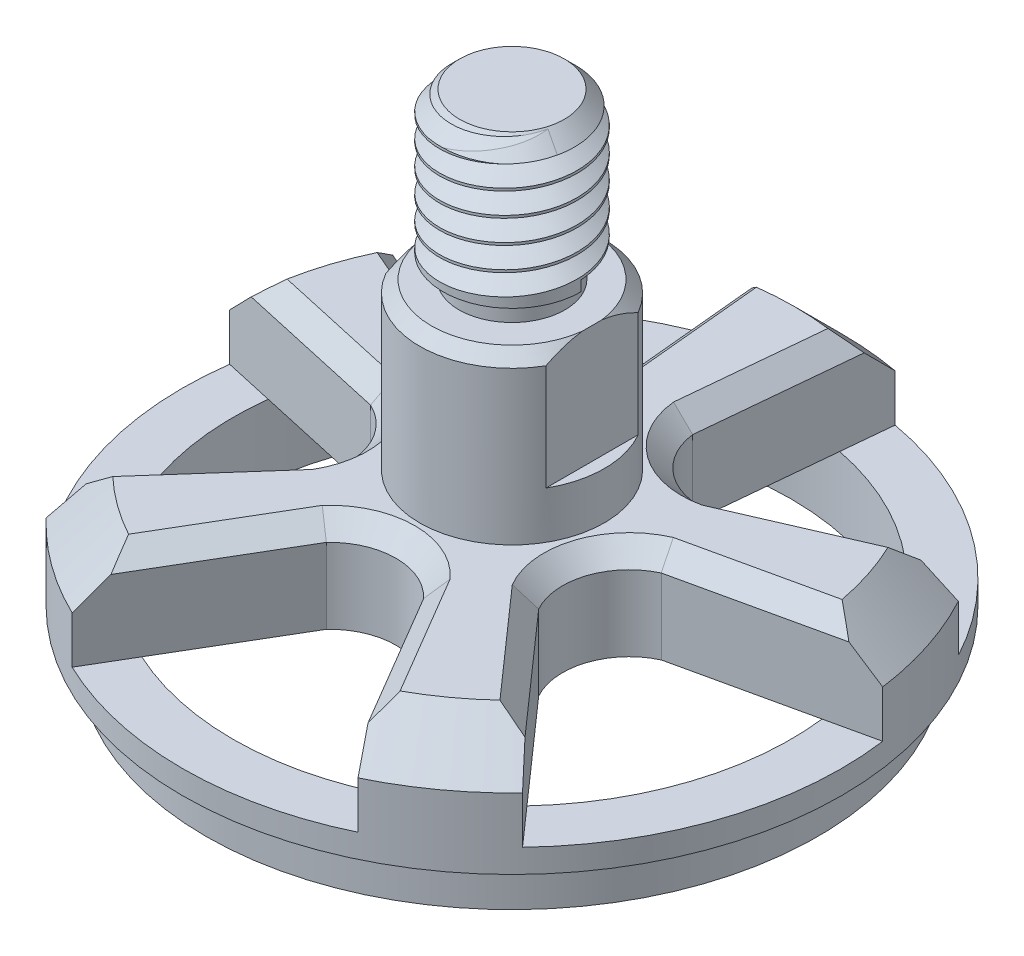
SolidWorks part; units mm, degrees
material "Aleación 1060"
ref_plane "Alzado" through (0, 0, 0) normal (0, 0, 1) x (1, 0, 0)
ref_plane "Planta" through (0, 0, 0) normal (0, 1, 0) x (1, 0, 0)
ref_plane "Vista lateral" through (0, 0, 0) normal (1, 0, 0) x (0, 0, -1)
sketch "Croquis1" plane through (0, 0, 0) normal (0, 1, 0) x (1, 0, 0)
  circle A0 centre (0, 0) radius 14
  circle A1 centre (0, 0) radius 11.85
  dimension "D1" = 28
  dimension "D2" = 23.7
extrude "Saliente-Extruir1" add sketch "Croquis1" against normal blind 1
sketch "Croquis3" plane through (0, 0, 0) normal (0, 1, 0) x (1, 0, 0)
  line L2 (5.0942, 3.4953) -> (12.3274, 6.6358)
  line L3 (6.1758, 0.1666) -> (13.8736, 1.8774)
  line L6 (4.8984, -3.7648) -> (10.1204, -9.6735)
  line L7 (-1.75, 5.925) -> (-2.5017, 13.7747)
  line L8 (1.75, 5.925) -> (2.5017, 13.7747)
  line L9 (2.0668, -5.822) -> (6.0727, -12.6144)
  line L11 (-2.0668, -5.822) -> (-6.0727, -12.6144)
  line L12 (-4.8984, -3.7648) -> (-10.1204, -9.6735)
  line L14 (-6.1758, 0.1666) -> (-13.8736, 1.8774)
  line L15 (-5.0942, 3.4953) -> (-12.3274, 6.6358)
  arc A0 (-10.1204, -9.6735) -> (-6.0742, -12.6137) centre (0, 0) ccw
  arc A1 (6.0727, -12.6144) -> (10.1193, -9.6747) centre (0, 0) ccw
  arc A2 (13.8736, 1.8774) -> (12.3282, 6.6343) centre (0, 0) ccw
  arc A3 (12.3282, 6.6343) -> (12.3274, 6.6358) centre (0, 0) ccw
  arc A4 (10.1193, -9.6747) -> (10.1204, -9.6735) centre (0, 0) ccw
  arc A5 (-6.0742, -12.6137) -> (-6.0727, -12.6144) centre (0, 0) ccw
  arc A6 (-13.8733, 1.8791) -> (-13.8736, 1.8774) centre (0, 0) ccw
  arc A7 (-12.3282, 6.6343) -> (-13.8733, 1.8791) centre (0, 0) ccw
  arc A8 (-5.0942, 3.4953) -> (-1.75, 5.925) centre (-4.558, 6.2736) ccw
  arc A9 (-6.1758, 0.1666) -> (-4.8984, -3.7648) centre (-7.375, -2.3963) cw
  arc A10 (-2.0668, -5.822) -> (2.0668, -5.822) centre (0, -7.7546) cw
  arc A11 (4.8984, -3.7648) -> (6.1758, 0.1666) centre (7.375, -2.3963) cw
  arc A12 (5.0942, 3.4953) -> (1.75, 5.925) centre (4.558, 6.2736) cw
  arc A13 (2.5017, 13.7747) -> (-2.5017, 13.7747) centre (0, 0) ccw
  arc A14 (-12.3274, 6.6358) -> (-12.3282, 6.6343) centre (0, 0) ccw
  point P51 (0, 0)
extrude "Saliente-Extruir2" add sketch "Croquis3" along normal blind 4
chamfer "Chaflán1" distance 0.8 angle 45 15 edges at (-4.0698, 4, 9.2182) (0, 4, 4.925) (4.0698, 4, 9.2182) (7.5094, 4, 6.7192) (4.684, 4, 1.5219) (10.0247, 4, -1.022) (8.7108, 4, -5.0656) (2.8948, 4, -3.9844) (2.1258, 4, -9.8498) (-7.5094, 4, 6.7192) (-4.684, 4, 1.5219) (-10.0247, 4, -1.022) (-2.1258, 4, -9.8498) (-2.8948, 4, -3.9844) (-8.7108, 4, -5.0656)
chamfer "Chaflán2" distance 2 distance2 2 5 edges at (-8.229, 4, 11.3262) (8.229, 4, 11.3262) (13.3148, 4, -4.3262) (0, 4, -14) (-13.3148, 4, -4.3262)
sketch "Croquis4" plane through (0, 4, 0) normal (0, 1, 0) x (1, 0, 0)
  circle A0 centre (0, 0) radius 3.925
  dimension "D1" = 7.85
extrude "Saliente-Extruir3" add sketch "Croquis4" along normal blind 7
chamfer "Chaflán3" distance 0.5 angle 45 1 edges at (0, 11, 3.925)
sketch "Croquis5" plane through (0, 11, 0) normal (0, 1, 0) x (1, 0, 0)
  circle A0 centre (0, 0) radius 2.925
  dimension "D1" = 5.85
extrude "Saliente-Extruir4" add sketch "Croquis5" along normal blind 7
chamfer "Chaflán4" distance 0.7 angle 45 1 edges at (0, 18, 2.925)
sketch "Croquis6" plane through (0, 0, 0) normal (0, -1, 0) x (1, 0, 0)
  circle A0 centre (0, 0) radius 3.5
extrude "Saliente-Extruir5" add sketch "Croquis6" along normal blind 1
sketch "Croquis7" plane through (0, -1, 0) normal (0, -1, 0) x (-1, 0, 0)
  circle A0 centre (0, 0) radius 1.5
extrude "Cortar-Extruir2" cut sketch "Croquis7" against normal blind 10
sketch "Croquis8" plane through (0, -1, 0) normal (0, -1, 0) x (1, 0, 0)
  circle A1 centre (0, 0) radius 11.85
  circle A2 centre (0, 0) radius 13
  circle A3 centre (0, 0) radius 13
  dimension "D1" = 1
extrude "Saliente-Extruir6" add sketch "Croquis8" along normal blind 2
sketch "Croquis11" plane through (0, 18, 0) normal (0, 1, 0) x (1, 0, 0)
  circle A0 centre (0, 0) radius 2.925
curve "Hélice/Espiral1" pitch 1 height 6 turns 6
sketch "Croquis12" plane through (0, 0, 0) normal (0, 0, 1) x (1, 0, 0)
  line L1 (3.4245, 17.2087) -> (2.2745, 17.9964)
  line L3 (0, 18.9744) -> (0, 15.037) construction
  line L4 (3.4245, 17.2087) -> (3.4245, 18.786)
  line L8 (2.2745, 17.9964) -> (3.4245, 18.786)
  dimension "D1" = 1.15
sweep "Cortar-Barrer3" cut profiles "Croquis12" path "Hélice/Espiral1" align with end faces yes
sketch "Croquis14" plane through (0, 0, 0) normal (0, 0, 1) x (1, 0, 0)
  line L0 (3.425, 11) -> (-3.425, 11) construction
  line L1 (3.4845, 12) -> (2.25, 12)
  line L2 (3.4845, 12) -> (3.4845, 11)
  line L3 (3.4845, 11) -> (2.25, 11)
  line L4 (2.25, 12) -> (2.25, 11)
  line L5 (0, 19.5407) -> (0, 8.0368) construction
  dimension "D1" = 1
  dimension "D2" = 2.25
revolve "Cortar-Revolución2" cut sketch "Croquis14" angle 360 about L5
sketch "Croquis15" plane through (0, 11, 0) normal (0, 1, 0) x (1, 0, 0)
  line L0 (0, 15.0388) -> (0, -18.8641) construction
  line L1 (3.925, 3.1932) -> (3.4, 3.1932)
  line L2 (3.925, 3.1932) -> (3.925, -3.4365)
  line L3 (3.925, -3.4365) -> (3.4, -3.4365)
  line L4 (3.4, 3.1932) -> (3.4, -3.4365)
  line L5 (-3.925, 4.3244) -> (-3.4, 4.3244)
  line L6 (-3.925, 4.3244) -> (-3.925, -3.925)
  line L7 (-3.925, -3.925) -> (-3.4, -3.925)
  line L8 (-3.4, 4.3244) -> (-3.4, -3.925)
  circle A0 centre (0, 0) radius 3.925 construction
  dimension "D1" = 3.4
  dimension "D2" = 3.4
extrude "Cortar-Extruir3" cut sketch "Croquis15" against normal blind 5
